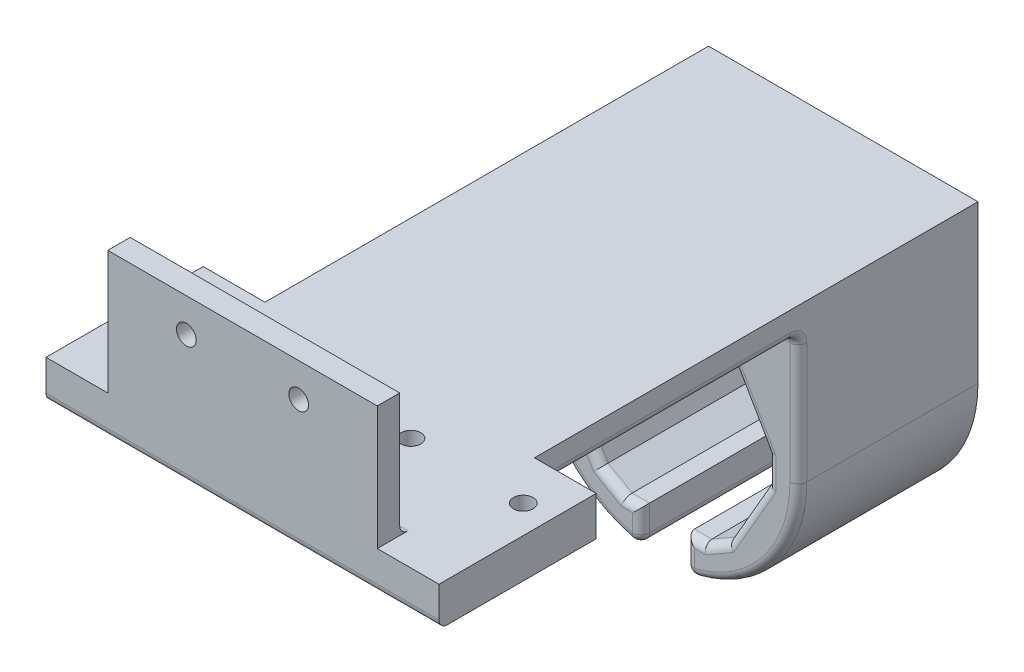
SolidWorks part; units mm, degrees
ref_plane "Front Plane" through (0, 0, 0) normal (1, 0, 0) x (0, 1, 0)
ref_plane "Top Plane" through (0, 0, 0) normal (0, 0, 1) x (0, 1, 0)
ref_plane "Right Plane" through (0, 0, 0) normal (0, 1, 0) x (-1, 0, 0)
sketch "Sketch1" plane through (0, 0, 0) normal (0, 0, 1) x (0, 1, 0)
  circle A0 centre (0, 0) radius 24
  dimension "D1" = 48
extrude "Boss-Extrude2" add sketch "Sketch1" along normal blind 32
sketch "Sketch2" plane through (0, 0, 32) normal (0, 0, 1) x (1, 0, 0)
  line L0 (0, 0) -> (-19.9053, 0) construction
  line L1 (7.1, 17.2385) -> (-7.0999, 17.2385)
  line L2 (-11.379, 14.768) -> (-18.4789, 2.4705)
  line L3 (-18.4789, -2.4705) -> (-11.379, -14.768)
  line L4 (-7.0999, -17.2385) -> (7.1, -17.2385)
  line L5 (11.379, -14.768) -> (18.479, -2.4705)
  line L6 (18.479, 2.4705) -> (11.379, 14.768)
  line L7 (-7.0999, 17.2385) -> (-11.379, 14.768)
  line L8 (11.379, 14.768) -> (7.1, 17.2385)
  line L9 (18.479, -2.4705) -> (18.479, 2.4705)
  line L10 (7.1, -17.2385) -> (11.379, -14.768)
  line L11 (-11.379, -14.768) -> (-7.0999, -17.2385)
  line L12 (-18.4789, 2.4705) -> (-18.4789, -2.4705)
  circle A0 centre (0, 0) radius 17.2385 construction
  point P2 (9.9527, 17.2385)
  point P3 (-9.9526, 17.2385)
  point P5 (-9.9526, -17.2385)
  point P6 (9.9527, -17.2385)
  point P7 (19.9053, 0)
  dimension "D1" = 19.9053
extrude "Cut-Extrude1" cut sketch "Sketch2" against normal blind 28
sketch "Sketch3" plane through (0, 0, 0) normal (0, 0, -1) x (1, 0, 0)
  line L1 (-4, -4) -> (4, -4)
  line L2 (-4, -4) -> (-4, 4)
  line L3 (-4, 4) -> (4, 4)
  line L4 (4, -4) -> (4, 4)
  line L5 (-4, -4) -> (4, 4) construction
  line L6 (-4, 4) -> (4, -4) construction
  point P0 (0, 0)
  dimension "D1" = 8
extrude "Cut-Extrude2" cut sketch "Sketch3" against normal up to next
sketch "Sketch4" plane through (0, 0, 32) normal (0, 0, 1) x (1, 0, 0)
  line L0 (-24, 0) -> (-24, 28)
  line L1 (-24, 28) -> (24, 28)
  line L2 (24, 28) -> (24, 0)
  line L3 (-24, 0) -> (-22, 0)
  line L4 (22, 0) -> (24, 0)
  circle A0 centre (0, 0) radius 24 construction
  arc A2 (-22, 0) -> (22, 0) centre (0, 0) cw
  dimension "D1" = 2
  dimension "D2" = 28
extrude "Boss-Extrude3" add sketch "Sketch4" against normal up to surface (32 mm away) up to face at (0, 0, 0)
sketch "Sketch6" plane through (0, 0, 32) normal (0, 0, 1) x (1, 0, 0)
  line L0 (24, 0) -> (24, 28) construction
  line L1 (-24, 28) -> (24, 28)
  line L2 (-24, 28) -> (-24, 23)
  line L3 (-24, 23) -> (24, 23)
  line L4 (24, 28) -> (24, 23)
  dimension "D1" = 5
extrude "Boss-Extrude4" add sketch "Sketch6" along normal blind 75
sketch "Sketch7" plane through (0, 28, 0) normal (0, 1, 0) x (-1, 0, 0)
  line L0 (24, 0) -> (24, 107) construction
  line L1 (-24, 107) -> (24, 107)
  line L2 (-24, 107) -> (-24, 103)
  line L3 (-24, 103) -> (24, 103)
  line L4 (24, 107) -> (24, 103)
  dimension "3" = 4
extrude "Boss-Extrude5" add sketch "Sketch7" along normal blind 22
sketch "Sketch8" plane through (0, 0, 103) normal (0, 0, -1) x (1, 0, 0)
  line L0 (24, -50) -> (-24, -50) construction
  line L1 (0, -50) -> (0, -28) construction
  line L2 (24, -28) -> (-24, -28) construction
  line L3 (0, -44) -> (-24, -44) construction
  line L4 (-24, -50) -> (-24, -28) construction
  line L5 (-24, -28) -> (24, -28) construction
  circle A1 centre (-10, -44) radius 1.75
  circle A2 centre (10, -44) radius 1.75
  dimension "D1" = 3.5
  dimension "D2" = 10
  dimension "D3" = 16
extrude "Cut-Extrude3" cut sketch "Sketch8" against normal up to next
sketch "Sketch9" plane through (0, 28, 0) normal (0, 1, 0) x (-1, 0, 0)
  line L0 (0, 103) -> (0, 0) construction
  line L1 (-24, 103) -> (24, 103) construction
  line L2 (0, 87) -> (-24, 87) construction
  line L3 (-24, 0) -> (-24, 103) construction
  line L4 (-24, 103) -> (24, 103) construction
  circle A1 centre (-20, 87) radius 1.85
  circle A2 centre (20, 87) radius 1.85
  dimension "D1" = 16
  dimension "D2" = 20
extrude "Cut-Extrude4" [suppressed] cut sketch "Sketch9" against normal up to next
sketch "Sketch11" plane through (0, 23, 0) normal (0, -1, 0) x (1, 0, 0)
  line L0 (-24, 107) -> (24, 107) construction
  line L1 (-35, 107) -> (35, 107)
  line L2 (-35, 107) -> (-35, 79)
  line L3 (-35, 79) -> (35, 79)
  line L4 (35, 107) -> (35, 79)
  line L5 (0, 0) -> (0, 107) construction
  dimension "D1" = 28
  dimension "D2" = 70
extrude "Boss-Extrude7" add sketch "Sketch11" against normal blind 5 and the other way blind 2
sketch "Sketch12" plane through (0, 28, 0) normal (0, 1, 0) x (-1, 0, 0)
  line L0 (0, 103) -> (0, 107) construction
  line L1 (-24, 103) -> (24, 103) construction
  line L2 (24, 107) -> (-24, 107) construction
  line L3 (-35, 87) -> (35, 87) construction
  line L4 (-35, 79) -> (-35, 107) construction
  line L5 (35, 107) -> (35, 79) construction
  line L6 (-24, 103) -> (24, 103) construction
  circle A0 centre (-10, 87) radius 1.75
  circle A1 centre (-30, 87) radius 1.75
  circle A2 centre (10, 87) radius 1.75
  circle A3 centre (30, 87) radius 1.75
  dimension "D4" = 3.5
  dimension "D1" = 16
  dimension "D2" = 20
  dimension "D3" = 10
extrude "Cut-Extrude5" cut sketch "Sketch12" against normal up to next
sketch "Sketch13" plane through (0, 0, 32) normal (0, 0, 1) x (1, 0, 0)
  line L0 (-4, -4) -> (-4, -23.6643)
  line L1 (-4, -4) -> (4, -4)
  line L2 (4, -4) -> (4, -23.6643)
  line L3 (4, -4) -> (-4, -4) construction
  line L4 (-4, -4) -> (-4, 4) construction
  line L5 (4, 4) -> (4, -4) construction
  arc A0 (-24, 0) -> (24, 0) centre (0, 0) ccw construction
  arc A1 (4, -23.6643) -> (-4, -23.6643) centre (0, 0) cw
extrude "Cut-Extrude6" cut sketch "Sketch13" against normal through all
fillet "Fillet2" radius 1.5 26 edges at (0, 23, 32) (0, 21, 107) (0, 28, 103) (-24, 23, 55.5) (24, 23, 55.5) (9.2395, -16.0032, 32) (14.929, -8.6192, 32) (18.479, 0, 32) (14.929, 8.6192, 32) (9.2395, 16.0032, 32) (0, 17.2385, 32) (-9.2395, 16.0032, 32) (-14.929, 8.6192, 32) (-18.4789, 0, 32) (-14.929, -8.6192, 32) (-9.2395, -16.0032, 32) (-4, -20.4514, 32) (-18.3303, -15.4919, 32) (-24, 11.5, 32) (24, 11.5, 32) (18.3303, -15.4919, 32) (4, -20.4514, 32) (4, -23.6643, 16) (-4, -23.6643, 16) (5.55, -17.2385, 32) (-5.55, -17.2385, 32)
fillet "Fillet3" radius 4 2 edges at (-4, 4, 2) (4, 4, 2)
